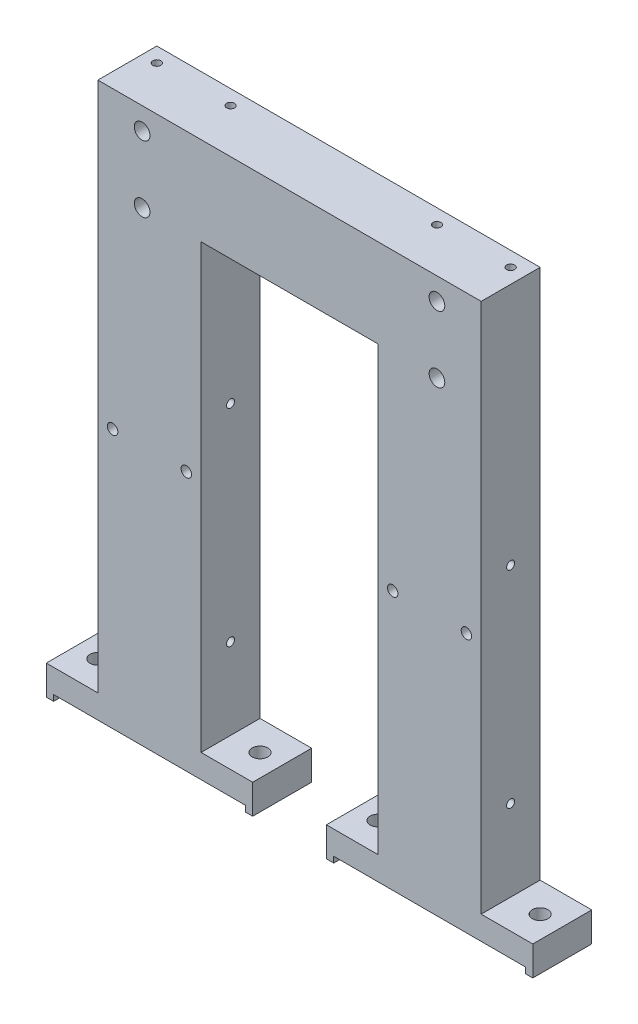
SolidWorks part; units mm, degrees
material "6061 Alloy"
ref_plane "Front Plane" through (0, 0, 0) normal (0, 0, 1) x (1, 0, 0)
ref_plane "Top Plane" through (0, 0, 0) normal (0, 1, 0) x (1, 0, 0)
ref_plane "Right Plane" through (0, 0, 0) normal (1, 0, 0) x (0, 0, -1)
sketch "Sketch1" plane through (0, 0, 0) normal (0, 0, 1) x (1, 0, 0)
  line L1 (-82.55, -120.65) -> (82.55, -120.65)
  line L2 (-82.55, -120.65) -> (-82.55, 120.65)
  line L3 (-82.55, 120.65) -> (82.55, 120.65)
  line L4 (82.55, -120.65) -> (82.55, 120.65)
  line L5 (-82.55, -120.65) -> (82.55, 120.65) construction
  line L6 (-82.55, 120.65) -> (82.55, -120.65) construction
  point P0 (0, 0)
  dimension "D1" = 241.3
  dimension "D2" = 165.1
extrude "Boss-Extrude1" add sketch "Sketch1" along normal blind 25.4
sketch "Sketch2" plane through (0, 0, 25.4) normal (0, 0, 1) x (1, 0, 0)
  line L0 (-82.55, -120.65) -> (82.55, -120.65) construction
  line L1 (-38.1, -120.65) -> (38.1, -120.65)
  line L2 (-38.1, -120.65) -> (-38.1, 82.55)
  line L3 (-38.1, 82.55) -> (38.1, 82.55)
  line L4 (38.1, -120.65) -> (38.1, 82.55)
  line L5 (-82.55, 120.65) -> (-82.55, -120.65) construction
  line L6 (82.55, 120.65) -> (-82.55, 120.65) construction
  dimension "D1" = 203.2
  dimension "D2" = 76.2
  dimension "D3" = 44.45
  dimension "D4" = 38.1
extrude "Cut-Extrude1" cut sketch "Sketch2" against normal through all
sketch "Sketch7" plane through (0, 0, 25.4) normal (0, 0, 1) x (1, 0, 0)
  line L0 (-82.55, -120.65) -> (-38.1, -120.65) construction
  line L1 (-104.775, -107.95) -> (-15.875, -107.95)
  line L2 (-104.775, -107.95) -> (-104.775, -120.65)
  line L3 (-104.775, -120.65) -> (-15.875, -120.65)
  line L4 (-15.875, -107.95) -> (-15.875, -120.65)
  line L5 (-104.775, -107.95) -> (-15.875, -120.65) construction
  line L6 (-104.775, -120.65) -> (-15.875, -107.95) construction
  line L7 (-82.55, 120.65) -> (-82.55, -120.65) construction
  point P0 (-60.325, -114.3)
  dimension "D1" = 0
  dimension "D2" = 88.9
  dimension "D3" = 22.225
  dimension "D4" = 12.7
extrude "Boss-Extrude4" add sketch "Sketch7" against normal blind 25.4
sketch "Sketch8" plane through (0, -120.65, 0) normal (0, -1, 0) x (-1, 0, 0)
  line L0 (104.775, -25.4) -> (15.875, -25.4) construction
  line L1 (101.6, 0) -> (19.05, 0)
  line L2 (101.6, 0) -> (101.6, -25.4)
  line L3 (101.6, -25.4) -> (19.05, -25.4)
  line L4 (19.05, 0) -> (19.05, -25.4)
  line L5 (101.6, 0) -> (19.05, -25.4) construction
  line L6 (101.6, -25.4) -> (19.05, 0) construction
  line L8 (104.775, 0) -> (104.775, -25.4) construction
  line L9 (15.875, 0) -> (15.875, -25.4) construction
  point P0 (60.325, -12.7)
  dimension "D1" = 25.4
  dimension "D2" = 3.175
  dimension "D3" = 3.175
extrude "Cut-Extrude4" cut sketch "Sketch8" against normal blind 2.54
mirror "Mirror3" about plane through (0, 0, 0) normal (1, 0, 0) of "Cut-Extrude4", "Boss-Extrude4"
hole_wizard "1/4 Clearance Hole1" positions "Sketch12" profile "Sketch13" hole size "1/4" standard "ANSI Inch" end condition up to next
sketch "Sketch12" plane through (0, -107.95, 0) normal (0, 1, 0) x (1, 0, 0)
  line L0 (-104.775, 0) -> (-104.775, -25.4) construction
  line L1 (-82.55, 0) -> (-104.775, 0) construction
  line L2 (-15.875, 0) -> (-38.1, 0) construction
  line L3 (-15.875, 0) -> (-15.875, -25.4) construction
  line L4 (15.875, 0) -> (15.875, -25.4) construction
  line L5 (15.875, 0) -> (38.1, 0) construction
  line L6 (82.55, 0) -> (104.775, 0) construction
  line L7 (104.775, 0) -> (104.775, -25.4) construction
  point P0 (-95.25, -12.7)
  point P2 (-25.4, -12.7)
  point P4 (25.4, -12.7)
  point P6 (95.25, -12.7)
  dimension "D1" = 9.525
  dimension "D2" = 12.7
  dimension "D3" = 12.7
  dimension "D4" = 9.525
  dimension "D5" = 9.525
  dimension "D6" = 12.7
  dimension "D7" = 12.7
  dimension "D8" = 9.525
sketch "Sketch13" plane through (-95.25, -107.95, 12.7) normal (1, 0, 0) x (0, 0, 1)
  line L0 (0, 0) -> (0, 10.16)
  line L1 (0, 10.16) -> (3.3782, 10.16)
  line L2 (3.3782, 10.16) -> (3.3782, 0)
  line L5 (3.3782, 0) -> (0, 0)
  line L11 (0, -6.35) -> (0, 107.95) construction
  dimension "Thru Hole Dia." = 6.7564
  dimension "Thru Hole Depth" = 10.16
hole_wizard "CBORE for 1/4 Socket Head Cap Screw1" positions "Sketch20" profile "Sketch21" counterbore size "1/4" standard "ANSI Inch" end condition through all
sketch "Sketch20" plane through (0, 0, 0) normal (0, 0, -1) x (-1, 0, 0)
  line L0 (-82.55, 120.65) -> (82.55, 120.65) construction
  line L1 (-82.55, -107.95) -> (-82.55, 120.65) construction
  line L2 (82.55, 120.65) -> (82.55, -107.95) construction
  point P0 (-63.5, 111.125)
  point P2 (-63.5, 82.55)
  point P4 (63.5, 111.125)
  point P6 (63.5, 82.55)
  dimension "D1" = 9.525
  dimension "D2" = 28.575
  dimension "D3" = 9.525
  dimension "D4" = 28.575
  dimension "D5" = 19.05
  dimension "D6" = 19.05
  dimension "D7" = 19.05
  dimension "D8" = 19.05
sketch "Sketch21" plane through (63.5, 111.125, 0) normal (1, 0, 0) x (0, 1, 0)
  line L0 (0, 0) -> (0, 25.4)
  line L1 (0, 25.4) -> (3.3782, 25.4)
  line L3 (3.3782, 25.4) -> (3.3782, 6.35)
  line L4 (3.3782, 6.35) -> (5.5562, 6.35)
  line L5 (5.5562, 6.35) -> (5.5562, 0)
  line L7 (5.5562, 0) -> (0, 0)
  line L11 (0, -6.35) -> (0, 107.95) construction
  dimension "Thru Hole Dia." = 6.7564
  dimension "Thru Hole Depth" = 25.4
  dimension "C'Bore Dia." = 11.1125
  dimension "C'Bore Depth" = 6.35
hole_wizard "#8-32 Tapped Hole1" positions "Sketch22" profile "Sketch23" tap size "#8-32" standard "ANSI Inch"
sketch "Sketch22" plane through (0, 120.65, 0) normal (0, 1, 0) x (1, 0, 0)
  line L0 (-82.55, -25.4) -> (-82.55, 0) construction
  line L1 (82.55, -25.4) -> (82.55, 0) construction
  line L2 (82.55, -25.4) -> (-82.55, -25.4) construction
  point P0 (-76.2, -6.35)
  point P2 (-44.45, -6.35)
  point P4 (44.45, -6.35)
  point P6 (76.2, -6.35)
  dimension "D1" = 6.35
  dimension "D2" = 38.1
  dimension "D3" = 38.1
  dimension "D4" = 6.35
  dimension "D5" = 19.05
  dimension "D6" = 19.05
  dimension "D7" = 19.05
  dimension "D8" = 19.05
cosmetic thread "Hole Thread1" parameters "D1"=8.382, "D2"=4.1656
cosmetic thread "Hole Thread2" parameters "D1"=8.382, "D2"=4.1656
cosmetic thread "Hole Thread3" parameters "D1"=8.382, "D2"=4.1656
cosmetic thread "Hole Thread4" parameters "D1"=8.382, "D2"=4.1656
sketch "Sketch23" plane through (-76.2, 120.65, 6.35) normal (1, 0, 0) x (0, 0, 1)
  line L0 (0, 0) -> (0, 13.7378)
  line L1 (0, 13.7378) -> (1.7272, 12.7)
  line L2 (1.7272, 12.7) -> (1.7272, 0)
  line L5 (1.7272, 0) -> (0, 0)
  line L10 (0, 13.7378) -> (-1.7272, 12.7) construction
  line L11 (0, -6.35) -> (0, 107.95) construction
  dimension "Tap Drill Dia." = 3.4544
  dimension "Tap Drill Depth" = 12.7
  dimension "Drill Angle" = 118
hole_wizard "CBORE for #8 Socket Head Cap Screw1" positions "Sketch24" profile "Sketch25" counterbore size "#8" standard "ANSI Inch" end condition through all
sketch "Sketch24" plane through (0, 0, 0) normal (0, 0, -1) x (-1, 0, 0)
  line L0 (-82.55, 120.65) -> (82.55, 120.65) construction
  line L1 (-82.55, -107.95) -> (-82.55, 120.65) construction
  line L2 (38.1, 82.55) -> (38.1, -107.95) construction
  line L3 (82.55, 120.65) -> (82.55, -107.95) construction
  point P0 (-76.2, -6.35)
  point P2 (-44.45, -6.35)
  point P4 (44.45, -6.35)
  point P6 (76.2, -6.35)
  dimension "D1" = 127
  dimension "D2" = 127
  dimension "D3" = 127
  dimension "D4" = 127
  dimension "D5" = 6.35
  dimension "D6" = 31.75
  dimension "D7" = 6.35
  dimension "D8" = 6.35
sketch "Sketch25" plane through (76.2, -6.35, 0) normal (1, 0, 0) x (0, 1, 0)
  line L0 (0, 0) -> (0, 25.4)
  line L1 (0, 25.4) -> (2.2479, 25.4)
  line L3 (2.2479, 25.4) -> (2.2479, 4.1656)
  line L4 (2.2479, 4.1656) -> (3.9687, 4.1656)
  line L5 (3.9687, 4.1656) -> (3.9687, 0)
  line L7 (3.9687, 0) -> (0, 0)
  line L11 (0, -6.35) -> (0, 107.95) construction
  dimension "Thru Hole Dia." = 4.4958
  dimension "Thru Hole Depth" = 25.4
  dimension "C'Bore Dia." = 7.9375
  dimension "C'Bore Depth" = 4.1656
hole_wizard "#8-32 Tapped Hole2" positions "Sketch26" profile "Sketch27" tap size "#8-32" standard "ANSI Inch" end condition up to next
sketch "Sketch26" plane through (-82.55, 0, 0) normal (-1, 0, 0) x (0, 0, 1)
  line L0 (25.4, 120.65) -> (25.4, -107.95) construction
  line L1 (0, -120.65) -> (25.4, -120.65) construction
  point P0 (12.7, -73.025)
  point P2 (12.7, 15.875)
  dimension "D1" = 12.7
  dimension "D2" = 12.7
  dimension "D3" = 88.9
  dimension "D4" = 47.625
sketch "Sketch27" plane through (-82.55, -73.025, 12.7) normal (0, 1, 0) x (0, 0, 1)
  line L0 (0, 0) -> (0, 44.45)
  line L1 (0, 44.45) -> (1.7272, 44.45)
  line L2 (1.7272, 44.45) -> (1.7272, 0)
  line L5 (1.7272, 0) -> (0, 0)
  line L11 (0, -6.35) -> (0, 107.95) construction
  dimension "Thru Tap Drill Dia." = 3.4544
  dimension "Thru Tap Drill Depth" = 44.45
cosmetic thread "Hole Thread5" parameters "D2"=4.1656
cosmetic thread "Hole Thread6" parameters "D2"=4.1656
mirror "Mirror4" about plane through (0, 0, 0) normal (1, 0, 0) of "#8-32 Tapped Hole2"
